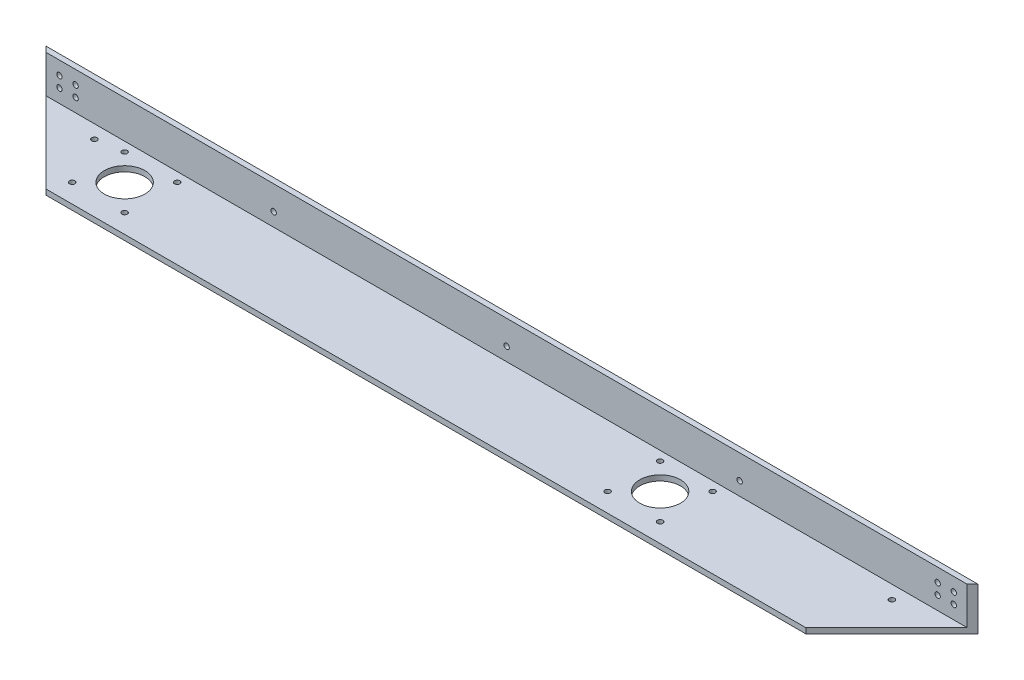
SolidWorks part; units mm, degrees
ref_plane "Front Plane" through (0, 0, 0) normal (0, 0, 1) x (1, 0, 0)
ref_plane "Top Plane" through (0, 0, 0) normal (0, 1, 0) x (1, 0, 0)
ref_plane "Right Plane" through (0, 0, 0) normal (1, 0, 0) x (0, 0, -1)
sketch "Sketch1" plane through (0, 0, 0) normal (1, 0, 0) x (0, 0, -1)
  line L0 (0, 0) -> (-50.8, 0)
  line L1 (-50.8, 0) -> (-50.8, 3.175)
  line L2 (-50.8, 3.175) -> (-3.175, 3.175)
  line L3 (-3.175, 3.175) -> (-3.175, 25.4)
  line L4 (-3.175, 25.4) -> (0, 25.4)
  line L5 (0, 25.4) -> (0, 0)
  dimension "LHeight" = 25.4
  dimension "LWidth" = 50.8
  dimension "LMaterialThickness" = 3.175
  dimension "D1" = 47.625
  dimension "D2" = 22.225
  dimension "D3" = 3.175
extrude "Boss-Extrude1" add sketch "Sketch1" along normal blind 550
chamfer "Chamfer7" distance 50.8 angle 45 1 edges at (0, 1.5875, 50.8)
chamfer "Chamfer8" distance 50.8 angle 45 1 edges at (550, 1.5875, 50.8)
sketch "BotthomHoles-Sketch2" plane through (0, 3.175, 0) normal (0, 1, 0) x (1, 0, 0)
  line L0 (546.825, -3.175) -> (3.175, -3.175) construction
  line L1 (550, 0) -> (0, 0) construction
  circle A0 centre (70.575, -24.175) radius 12
  circle A1 centre (386.575, -24.175) radius 12
  circle A2 centre (55.075, -8.675) radius 1.5875
  circle A3 centre (86.075, -8.675) radius 1.5875
  circle A4 centre (371.075, -8.675) radius 1.5875
  circle A5 centre (402.075, -8.675) radius 1.5875
  circle A6 centre (55.075, -39.675) radius 1.5875
  circle A7 centre (86.075, -39.675) radius 1.5875
  circle A8 centre (371.075, -39.675) radius 1.5875
  circle A9 centre (402.075, -39.675) radius 1.5875
  circle A10 centre (39.6875, -11.1125) radius 1.5875
  circle A11 centre (510.3125, -11.1125) radius 1.5875
  dimension "D9" = 3.175
  dimension "D10" = 24
  dimension "D14" = 3.175
  dimension "D2" = 8.675
  dimension "D3" = 31
  dimension "D4" = 15.5
  dimension "D5" = 15.5
  dimension "D6" = 31
  dimension "D7" = 15.5
  dimension "D8" = 31
  dimension "D11" = 21
  dimension "D12" = 316
  dimension "D13" = 70.575
  dimension "D15" = 39.6875
  dimension "D16" = 11.1125
  dimension "D17" = 39.6875
extrude "BottomHoles-Cut-Extrude1" cut sketch "BotthomHoles-Sketch2" against normal through all
sketch "LeftSideHoles-Sketch3" plane through (0, 0, 0) normal (0, 0, -1) x (-1, 0, 0)
  line L1 (-550, 0) -> (-550, 25.4) construction
  circle A0 centre (-538.8875, 17.4625) radius 1.5875
  circle A1 centre (-529.3625, 17.4625) radius 1.5875
  circle A2 centre (-538.8875, 11.1125) radius 1.5875
  circle A3 centre (-529.3625, 11.1125) radius 1.5875
  circle A4 centre (-11.1125, 11.1125) radius 1.5875
  circle A5 centre (-20.6375, 11.1125) radius 1.5875
  circle A6 centre (-20.6375, 17.4625) radius 1.5875
  circle A7 centre (-11.1125, 17.4625) radius 1.5875
  circle A8 centre (-412.5, 11.1125) radius 1.5875
  circle A9 centre (-275, 11.1125) radius 1.5875
  circle A10 centre (-137.5, 11.1125) radius 1.5875
  dimension "D7" = 3.175
  dimension "D1" = 11.1125
  dimension "D2" = 20.6375
  dimension "D3" = 7.9375
  dimension "D4" = 11.1125
  dimension "D5" = 11.1125
  dimension "D6" = 20.6375
  dimension "D8" = 137.5
  dimension "D9" = 137.5
  dimension "D10" = 137.5
extrude "LeftSideHoles-Cut-Extrude2" cut sketch "LeftSideHoles-Sketch3" against normal through all
equation "\"LowerRailWidth\"= 2.00in"
equation "\"LowerRailHeight\"= 1.00in"
equation "\"RailThickness\"= .125in'Spec"
equation "\"SideRailHoleY1FromEdge\"= \"HoleOffsetFromEdge\""
equation "\"SideRailHoleX1FromSide\"= \"HoleOffsetFromSide\""
equation "\"StepperHoleDiameter\"= 24mm"
equation "\"StepperMountingHoleDiameter\"= 3.175mm"
equation "\"SideRailLength\"= 550mm"
equation "\"StepperMountingHoleDistance\"= 31mm'Spec"
equation "\"VSWidth\"= 1.25in'Spec"
equation "\"StepperMountingHoleOffsetFromLeftOrRightSide\"= \"StepperMountingHoleOffsetFromItsSide\" + \"RailThickness\""
equation "\"HoleOffsetFromEdge\"= \"RailThickness\" * 2.5"
equation "\"HoleOffsetFromSide\"= \"RailThickness\" * 3.5"
equation "\"StepperMountingHoleOffsetFromItsSide\"= 5.5mm'Spec"
equation "\"SideRailHoleX2FromSide\"= \"VSWidth\" - \"HoleOffsetFromEdge\" - \"RailThickness\"'Equals 20.6375"
equation "\"FasteningHoleDiameter\"= .125in"
equation "\"SideRailHoleY2FromSide\"= \"HoleOffsetFromSide\""
equation "\"LHeight@Sketch1\"=\"LowerRailHeight\""
equation "\"LWidth@Sketch1\"=\"LowerRailWidth\""
equation "\"D1@Chamfer7\"=\"LowerRailWidth\""
equation "\"D1@Chamfer8\"=\"LowerRailWidth\""
equation "\"D2@BotthomHoles-Sketch2\" = \"StepperMountingHoleOffsetFromLeftOrRightSide\""
equation "\"D3@BotthomHoles-Sketch2\" = \"StepperMountingHoleDistance\""
equation "\"D4@BotthomHoles-Sketch2\" = \"StepperMountingHoleDistance\" / 2"
equation "\"D5@BotthomHoles-Sketch2\"= \"StepperMountingHoleDistance\" / 2"
equation "\"D6@BotthomHoles-Sketch2\" = \"StepperMountingHoleDistance\""
equation "\"D7@BotthomHoles-Sketch2\" = \"StepperMountingHoleDistance\" / 2"
equation "\"D8@BotthomHoles-Sketch2\" = \"StepperMountingHoleDistance\""
equation "\"D9@BotthomHoles-Sketch2\" = \"StepperMountingHoleDiameter\""
equation "\"D10@BotthomHoles-Sketch2\" = \"StepperHoleDiameter\""
equation "\"D1@LeftSideHoles-Sketch3\" = \"SideRailHoleX1FromSide\""
equation "\"D2@LeftSideHoles-Sketch3\" = \"SideRailHoleX2FromSide\""
equation "\"D3@LeftSideHoles-Sketch3\" = \"SideRailHoleY1FromEdge\""
equation "\"D4@LeftSideHoles-Sketch3\" = \"SideRailHoleY2FromSide\""
equation "\"D7@LeftSideHoles-Sketch3\" = \"FasteningHoleDiameter\""
equation "\"D1@Boss-Extrude1\"=\"SideRailLength\""
equation "\"D5@LeftSideHoles-Sketch3\"=\"SideRailHoleX1FromSide\""
equation "\"D6@LeftSideHoles-Sketch3\"=\"SideRailHoleX2FromSide\""
equation "\"DistanceBetweenFrontToBackStepperHoles\"= \"BedLength\" - \"DistanceFromBedFrontToFirstLeftStepperHole\"'Equals 316"
equation "\"BedOverlap\"= 20mm"
equation "\"BedThirdSize\"= 70mm"
equation "\"BedLWidth\"= \"BedThirdSize\" + \"BedOverlap\"'Equals 90"
equation "\"BedInnerSquareWidth\"= \"BedThirdSize\" * 3'Equals 210"
equation "\"BedInnerSquareLength\"= \"BedInnerSquareWidth\""
equation "\"BedLength\"= \"BedInnerSquareLength\" + \"BedLWidth\" * 2 - \"BedOverlap\" * 2 + \"BedIncreasedByLength\"'Equals 350"
equation "\"D12@BotthomHoles-Sketch2\"=\"DistanceBetweenFrontToBackStepperHoles\""
equation "\"DistanceFromFrontSideToFirstLeftStepperHole\"= \"DistanceFromFrontSideToBedFront\" + \"DistanceFromBedFrontToFirstLeftStepperHole\"'Equals 70.575"
equation "\"D13@BotthomHoles-Sketch2\"=\"DistanceFromFrontSideToFirstLeftStepperHole\""
equation "\"DistanceFromBedFrontToFirstLeftStepperHole\"= \"LeadScrewNutPadSize\" + 10mm'Equals 34"
equation "\"DistanceFromFrontSideToBedFront\"= \"RailThickness\" + \"BeltTensionerDepth\" + 10mm'Equals 36.575"
equation "\"BeltTensionerDepth\"= \"BeltTensionerBackWallThickness\" + \"BeltTensionerInnerDepth\"'Equals 23.4"
equation "\"BeltTensionerBackWallThickness\"= 4mm"
equation "\"20TGT2PulleyDiameter\"= 17.9mm'Spec"
equation "\"BeltTensionerSpaceBetweenPulleyAndWall\"= 1.5mm"
equation "\"BeltTensionerInnerDepth\"= \"20TGT2PulleyDiameter\" + \"BeltTensionerSpaceBetweenPulleyAndWall\""
equation "\"BedIncreasedByLength\"= 0mm"
equation "\"LowerCornerBlockWidth\"= \"LowerRailWidth\" - \"RailThickness\" * 2'Room for left front stepper"
equation "\"D14@BotthomHoles-Sketch2\"= \"FasteningHoleDiameter\""
equation "\"D15@BotthomHoles-Sketch2\"=\"LowerCornerBlockX1FromSide\""
equation "\"D16@BotthomHoles-Sketch2\"= \"LowerCornerBlockY1FromSide\""
equation "\"D17@BotthomHoles-Sketch2\"=\"LowerCornerBlockX1FromSide\""
equation "\"LowerCornerBlockY1FromSide\"= \"HoleOffsetFromSide\""
equation "\"LowerCornerBlockX1FromSide\"= \"LowerCornerBlockWidth\" - \"HoleOffsetFromEdge\" + \"RailThickness\""
equation "\"LeadScrewNutMountingHoleFlangeDiameter\"= 22mm'Spec"
equation "\"LeadScrewNutPadSize\"= \"LeadScrewNutMountingHoleFlangeDiameter\" + 2mm'Equals 24"
equation "\"LeftOrRightEnclosureOffsets\"= \"SideRailLength\" / 4"
equation "\"D8@LeftSideHoles-Sketch3\"=\"LeftOrRightEnclosureOffsets\""
equation "\"D9@LeftSideHoles-Sketch3\"=\"LeftOrRightEnclosureOffsets\""
equation "\"D10@LeftSideHoles-Sketch3\"=\"LeftOrRightEnclosureOffsets\""
